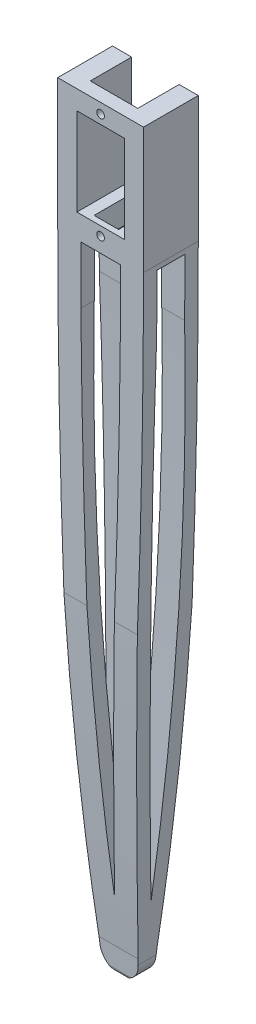
SolidWorks part; units mm, degrees
ref_plane "Front Plane" through (0, 0, 0) normal (0, 0, 1) x (1, 0, 0)
ref_plane "Top Plane" through (0, 0, 0) normal (0, 1, 0) x (1, 0, 0)
ref_plane "Right Plane" through (0, 0, 0) normal (1, 0, 0) x (0, 0, -1)
sketch "Sketch1" plane through (0, 0, 0) normal (0, 0, 1) x (1, 0, 0)
  line L0 (0, -16.45) -> (0, -173.55) construction
  line L1 (-6.2, 16.45) -> (6.2, 16.45)
  line L2 (-11.2, 11.45) -> (-11.2, -16.45)
  line L4 (11.2, 11.45) -> (11.2, -16.45)
  line L5 (-11.2, 16.45) -> (11.2, -16.45) construction
  line L6 (-11.2, -16.45) -> (11.2, 16.45) construction
  arc A1 (-5, -178.55) -> (5, -178.55) centre (0, -178.55) ccw
  arc A2 (-11.2, -16.45) -> (-5, -178.55) centre (2110.9653, -16.45) ccw
  arc A3 (11.2, -16.45) -> (5, -178.55) centre (-2110.9653, -16.45) cw
  arc A4 (11.2, 11.45) -> (6.2, 16.45) centre (6.2, 11.45) ccw
  arc A5 (-6.2, 16.45) -> (-11.2, 11.45) centre (-6.2, 11.45) ccw
  point P0 (0, 0)
  dimension "D4" = 5
  dimension "D1" = 32.9
  dimension "D2" = 22.4
  dimension "D3" = 162.1
extrude "Boss-Extrude2" add sketch "Sketch1" along normal blind 5
sketch "Sketch4" plane through (0, 0, 5) normal (0, 0, 1) x (1, 0, 0)
  line L1 (-6.2, 11.45) -> (6.2, 11.45)
  line L2 (-6.2, 11.45) -> (-6.2, -11.45)
  line L3 (-6.2, -11.45) -> (6.2, -11.45)
  line L4 (6.2, 11.45) -> (6.2, -11.45)
  line L5 (-6.2, 11.45) -> (6.2, -11.45) construction
  line L6 (-6.2, -11.45) -> (6.2, 11.45) construction
  point P0 (0, 0)
  dimension "D1" = 22.9
  dimension "D2" = 12.4
extrude "Cut-Extrude1" cut sketch "Sketch4" against normal blind 5
sketch "Sketch5" plane through (0, 0, 5) normal (0, 0, 1) x (1, 0, 0)
  line L0 (0, 0) -> (0, 13.8) construction
  line L1 (0, 0) -> (0, -13.8) construction
  circle A0 centre (0, 13.8) radius 1
  circle A1 centre (0, -13.8) radius 1
  dimension "D1" = 13.8
  dimension "D2" = 13.8
extrude "Cut-Extrude2" cut sketch "Sketch5" against normal blind 5
sketch3d "3DSketch1"
  line L6 (-5.1604, -32.6864, 5) -> (5.1604, -32.6864, 5)
  spline S2 degree 5 poles (-5.1604, -32.6864, 5) (-5.1261, -37.5289, 5) (-5.0708, -42.3713, 5) (-4.9981, -47.2135, 5) (-4.7659, -60.1446, 5) (-4.4569, -73.0738, 5) (-4.2293, -81.1606, 5) (-3.6967, -97.3316, 5) (-2.9925, -113.496, 5) (-2.6018, -121.5766, 5) (-1.8933, -135.0415, 5) (-1.1015, -148.5022, 5) (-0.7667, -153.8853, 5) (-0.4048, -159.3358, 5) (-0.0148, -164.7842, 5) (-0.0099, -164.8531, 5) (-0.0049, -164.922, 5) (0, -164.9909, 5) knots 0.10922 0.10922 0.10922 0.10922 0.10922 0.10922 0.272094 0.272094 0.272094 0.544187 0.544187 0.544187 0.816281 0.816281 0.816281 0.997676 0.997676 0.997676 1 1 1 1 1 1
  spline S3 degree 5 poles (0, -164.9909, 5) (0.0049, -164.922, 5) (0.0099, -164.8531, 5) (0.0148, -164.7842, 5) (0.4048, -159.3358, 5) (0.7667, -153.8853, 5) (1.1015, -148.5022, 5) (1.8933, -135.0415, 5) (2.6018, -121.5766, 5) (2.9925, -113.496, 5) (3.6967, -97.3316, 5) (4.2293, -81.1606, 5) (4.4569, -73.0738, 5) (4.7659, -60.1446, 5) (4.9981, -47.2135, 5) (5.0708, -42.3713, 5) (5.1261, -37.5289, 5) (5.1604, -32.6864, 5) knots 0 0 0 0 0 0 0.002324 0.002324 0.002324 0.183719 0.183719 0.183719 0.455813 0.455813 0.455813 0.727906 0.727906 0.727906 0.89078 0.89078 0.89078 0.89078 0.89078 0.89078
extrude "Cut-Extrude3" cut sketch "3DSketch1" along direction (0, 0, -1) on the side against the normal blind 5
sketch "Sketch6" plane through (0, 0, 0) normal (0, 0, -1) x (-1, 0, 0)
  line L0 (0, 0) -> (-11.2, 0) construction
  line L1 (-11.2, -16.45) -> (-11.2, 11.45) construction
  line L2 (0, 0) -> (11.2, 0) construction
  line L3 (11.2, 11.45) -> (11.2, -16.45) construction
  line L4 (-11.2, 3.2511) -> (-6.2, 3.2511) construction
  line L5 (-6.2, -11.45) -> (-6.2, 11.45) construction
  line L6 (-8.7, 3.2511) -> (-8.7, 0) construction
  line L7 (6.2, 3.2511) -> (11.2, 3.2511) construction
  line L8 (6.2, 11.45) -> (6.2, -11.45) construction
  line L9 (8.7, 3.2511) -> (8.7, 0) construction
  line L11 (-11.2, 11.45) -> (-6.2, 11.45)
  line L12 (-11.2, 11.45) -> (-11.2, -11.45)
  line L13 (-11.2, -11.45) -> (-6.2, -11.45)
  line L14 (-6.2, 11.45) -> (-6.2, -11.45)
  line L15 (-11.2, 11.45) -> (-6.2, -11.45) construction
  line L16 (-11.2, -11.45) -> (-6.2, 11.45) construction
  line L17 (6.2, 11.45) -> (11.2, 11.45)
  line L18 (6.2, 11.45) -> (6.2, -11.45)
  line L19 (6.2, -11.45) -> (11.2, -11.45)
  line L20 (11.2, 11.45) -> (11.2, -11.45)
  line L21 (6.2, 11.45) -> (11.2, -11.45) construction
  line L22 (6.2, -11.45) -> (11.2, 11.45) construction
  dimension "D1" = 22.9
  dimension "D2" = 22.9
extrude "Boss-Extrude3" add sketch "Sketch6" along normal blind 12.3
sketch "Sketch7" plane through (0, 0, -12.3) normal (0, 0, -1) x (-1, 0, 0)
  line L0 (8.8805, 0) -> (8.8805, 6) construction
  circle A0 centre (-8.6658, 0) radius 1
  circle A1 centre (8.8805, 0) radius 1
  circle A2 centre (8.8805, 6) radius 1
  dimension "D1" = 6
extrude "Cut-Extrude4" cut sketch "Sketch7" against normal blind 5
sketch "Sketch8" plane through (0, 0, 0) normal (0, 0, -1) x (-1, 0, 0)
  line L15 (11.2, -16.45) -> (11.2, -11.45)
  line L16 (11.2, -11.45) -> (6.2, -11.45)
  line L17 (6.2, -11.45) -> (-6.2, -11.45)
  line L18 (-6.2, -11.45) -> (-11.2, -11.45)
  line L19 (-11.2, -11.45) -> (-11.2, -16.45)
  line L20 (11.2, -16.45) -> (11.2, -11.45)
  line L21 (11.2, -11.45) -> (6.2, -11.45)
  line L22 (6.2, -11.45) -> (-6.2, -11.45)
  line L23 (-6.2, -11.45) -> (-11.2, -11.45)
  line L24 (-11.2, -11.45) -> (-11.2, -16.45)
  arc A9 (-11.2, -16.45) -> (-5, -178.55) centre (2110.9653, -16.45) ccw
  arc A10 (-5, -178.55) -> (5, -178.55) centre (0, -178.55) ccw
  arc A11 (5, -178.55) -> (11.2, -16.45) centre (-2110.9653, -16.45) ccw
  arc A12 (-11.2, -16.45) -> (-5, -178.55) centre (2110.9653, -16.45) ccw
  arc A13 (-5, -178.55) -> (5, -178.55) centre (0, -178.55) ccw
  arc A14 (5, -178.55) -> (11.2, -16.45) centre (-2110.9653, -16.45) ccw
  dimension "D1" = 0
extrude "Boss-Extrude4" add sketch "Sketch8" along normal up to surface (12.3 mm away) up to face at (7.6658, 0, -12.3)
sketch "Sketch10" plane through (0, 0, 0) normal (0, 0, 1) x (1, 0, 0)
  line L2 (5.1604, -32.6864) -> (-5.1604, -32.6864)
  line L3 (5.1604, -32.6864) -> (-5.1604, -32.6864)
  spline S4 degree 5 poles (2742.061, 925.339) (1124.3728, 747.4592) (298.2396, 555.4175) (6.2629, 354.0921) (-9.5551, 140.2539) (-4.4569, -73.0738) (-4.2293, -81.1606) (-3.6967, -97.3316) (-2.9925, -113.496) (-2.6018, -121.5766) (-1.8933, -135.0415) (-1.1015, -148.5022) (-0.7667, -153.8853) (8.5195, -293.7189) (36.2296, -432.1823) (-203.7971, -585.1501) (-996.0841, -778.6215) (2070.6534, 438.815) knots -6.632632 -6.632632 -6.632632 -6.632632 -6.632632 -6.632632 0.272094 0.272094 0.272094 0.544187 0.544187 0.544187 0.816281 0.816281 0.816281 0.997676 0.997676 0.997676 5.529664 5.529664 5.529664 5.529664 5.529664 5.529664 only from (-5.1604, -32.6864) to (0, -164.9909)
  spline S5 degree 5 poles (-2591.2367, -1178.5003) (505.7514, -640.2869) (94.1134, -500.1546) (-26.7405, -381.6628) (-6.8269, -268.2322) (0.7667, -153.8853) (1.1015, -148.5022) (1.8933, -135.0415) (2.6018, -121.5766) (2.9925, -113.496) (3.6967, -97.3316) (4.2293, -81.1606) (4.4569, -73.0738) (9.5551, 140.2541) (-6.2629, 354.0925) (-298.2404, 555.4181) (-1124.376, 747.46) (-2742.0685, 925.3399) knots -3.670581 -3.670581 -3.670581 -3.670581 -3.670581 -3.670581 0.002324 0.002324 0.002324 0.183719 0.183719 0.183719 0.455813 0.455813 0.455813 0.727906 0.727906 0.727906 7.632639 7.632639 7.632639 7.632639 7.632639 7.632639 only from (0, -164.9909) to (5.1604, -32.6864)
  spline S6 degree 5 poles (-5.1604, -32.6864) (-5.1261, -37.5289) (-5.0708, -42.3713) (-4.9981, -47.2135) (-4.7659, -60.1446) (-4.4569, -73.0738) (-4.2293, -81.1606) (-3.6967, -97.3316) (-2.9925, -113.496) (-2.6018, -121.5766) (-1.8933, -135.0415) (-1.1015, -148.5022) (-0.7667, -153.8853) (-0.4048, -159.3358) (-0.0148, -164.7842) (-0.0099, -164.8531) (-0.0049, -164.922) (0, -164.9909) knots 0.10922 0.10922 0.10922 0.10922 0.10922 0.10922 0.272094 0.272094 0.272094 0.544187 0.544187 0.544187 0.816281 0.816281 0.816281 0.997676 0.997676 0.997676 1 1 1 1 1 1
  spline S7 degree 5 poles (0, -164.9909) (0.0049, -164.922) (0.0099, -164.8531) (0.0148, -164.7842) (0.4048, -159.3358) (0.7667, -153.8853) (1.1015, -148.5022) (1.8933, -135.0415) (2.6018, -121.5766) (2.9925, -113.496) (3.6967, -97.3316) (4.2293, -81.1606) (4.4569, -73.0738) (4.7659, -60.1446) (4.9981, -47.2135) (5.0708, -42.3713) (5.1261, -37.5289) (5.1604, -32.6864) knots 0 0 0 0 0 0 0.002324 0.002324 0.002324 0.183719 0.183719 0.183719 0.455813 0.455813 0.455813 0.727906 0.727906 0.727906 0.89078 0.89078 0.89078 0.89078 0.89078 0.89078
  dimension "D1" = 0
extrude "Cut-Extrude5" cut sketch "Sketch10" against normal blind 121
sketch "Sketch12" plane through (0, 0, 0) normal (1, 0, 0) x (0, 0, -1)
  line L2 (3.65, -183.55) -> (3.65, -164.9909) construction
  line L3 (-5, -183.55) -> (12.3, -183.55) construction
  line L6 (0, -32.6864) -> (7.3, -32.6864)
  line L7 (3.65, -32.6864) -> (3.65, -164.9909) construction
  arc A0 (0, -32.6864) -> (3.65, -164.9909) centre (1196.4285, -65.8821) ccw
  arc A1 (7.3, -32.6864) -> (3.65, -164.9909) centre (-1189.1285, -65.8821) cw
extrude "Cut-Extrude7" cut sketch "Sketch12" against normal through all
sketch "Sketch14" plane through (0, 0, 0) normal (1, 0, 0) x (0, 0, -1)
  line L0 (7.3, -32.6864) -> (0, -32.6864)
  arc A0 (7.3, -32.6864) -> (3.65, -164.9909) centre (-1189.1285, -65.8821) cw
  arc A1 (0, -32.6864) -> (3.65, -164.9909) centre (1196.4285, -65.8821) ccw
extrude "Cut-Extrude8" cut sketch "Sketch14" along normal blind 121
sketch "Sketch15" plane through (0, 0, 0) normal (1, 0, 0) x (0, 0, -1)
  line L6 (12.3019, -32.6864) -> (24.1567, -32.6864)
  line L7 (24.1567, -32.6864) -> (24.1567, -183.55)
  line L8 (24.1567, -183.55) -> (5.6261, -183.55)
  line L9 (-5.0019, -32.6864) -> (-15.6441, -32.6864)
  line L10 (-15.6441, -32.6864) -> (-15.6441, -183.55)
  line L11 (1.6739, -183.55) -> (-15.6441, -183.55)
  arc A2 (12.3019, -32.6864) -> (7.1191, -182.1952) centre (-1189.1285, -65.8821) cw
  arc A3 (-5.0019, -32.6864) -> (0.1809, -182.1952) centre (1196.4285, -65.8821) ccw
  arc A6 (5.6261, -183.55) -> (7.1191, -182.1952) centre (5.6261, -182.05) ccw
  arc A7 (1.6739, -183.55) -> (0.1809, -182.1952) centre (1.6739, -182.05) cw
  dimension "D2" = 1.5
extrude "Cut-Extrude12" cut sketch "Sketch15" against normal mid plane 121
sketch "Sketch16" plane through (0, -11.45, 0) normal (0, 1, 0) x (1, 0, 0)
  line L8 (-3.2, -2) -> (3.2, -2)
  line L9 (3.2, -2) -> (3.2, 9.3)
  line L10 (3.2, 9.3) -> (-3.2, 9.3)
  line L11 (-3.2, 9.3) -> (-3.2, -2)
  line L12 (-3.2, -2) -> (3.2, -2)
  line L13 (3.2, -2) -> (3.2, 9.3)
  line L14 (3.2, 9.3) -> (-3.2, 9.3)
  line L15 (-3.2, 9.3) -> (-3.2, -2)
  dimension "D1" = 3
extrude "Cut-Extrude13" cut sketch "Sketch16" against normal up to surface (21.2364 mm away) contours L12 L13 L14 L15
sketch "Sketch21" plane through (0, 0, 5) normal (0, 0, 1) x (1, 0, 0)
  line L0 (5.1604, -32.6864) -> (-5.1604, -32.6864) construction
  line L1 (0, -32.6864) -> (0, -17.6864) construction
  line L3 (-5.1604, -32.6864) -> (5.1604, -32.6864)
  line L4 (-5.1604, -32.6864) -> (-5.1604, -17.6864)
  line L5 (-5.1604, -17.6864) -> (5.1604, -17.6864)
  line L6 (5.1604, -32.6864) -> (5.1604, -17.6864)
  dimension "D1" = 15
extrude "Cut-Extrude14" cut sketch "Sketch21" against normal through all
sketch "Sketch23" plane through (-5.1604, 0, 0) normal (1, 0, 0) x (0, 0, -1)
  line L1 (0, -32.6864) -> (7.3, -32.6864)
  line L2 (0, -32.6864) -> (0, -17.6864)
  line L3 (0, -17.6864) -> (7.3, -17.6864)
  line L4 (7.3, -32.6864) -> (7.3, -17.6864)
  dimension "D1" = 15
extrude "Cut-Extrude15" cut sketch "Sketch23" against normal through all both and the other way through all
sketch "Sketch24" plane through (0, 11.45, 0) normal (0, 1, 0) x (1, 0, 0)
  line L1 (6.2, 0) -> (11.2, 0)
  line L2 (6.2, 0) -> (6.2, 12.3)
  line L3 (6.2, 12.3) -> (11.2, 12.3)
  line L4 (11.2, 0) -> (11.2, 12.3)
  line L5 (-6.2, 0) -> (-11.2, 0)
  line L6 (-6.2, 0) -> (-6.2, 12.3)
  line L7 (-6.2, 12.3) -> (-11.2, 12.3)
  line L8 (-11.2, 0) -> (-11.2, 12.3)
extrude "Boss-Extrude5" add sketch "Sketch24" along normal up to surface (5 mm away) up to face at (0, 16.45, 2.5)
sketch "Sketch25" plane through (11.2, 0, 0) normal (1, 0, 0) x (0, 0, -1)
  line L1 (-5, 11.45) -> (12.3, 11.45)
  line L2 (-5, 11.45) -> (-5, 16.45)
  line L3 (-5, 16.45) -> (12.3, 16.45)
  line L4 (12.3, 11.45) -> (12.3, 16.45)
extrude "Boss-Extrude6" add sketch "Sketch25" against normal up to next
sketch "Sketch26" plane through (-11.2, 0, 0) normal (-1, 0, 0) x (0, 0, 1)
  line L1 (5, 11.45) -> (0, 11.45)
  line L2 (5, 11.45) -> (5, 16.45)
  line L3 (5, 16.45) -> (0, 16.45)
  line L4 (0, 11.45) -> (0, 16.45)
extrude "Boss-Extrude7" add sketch "Sketch26" against normal up to next
sketch "Sketch27" plane through (0, 0, 5) normal (0, 0, 1) x (1, 0, 0)
sketch "Sketch28" plane through (6.2, 0, 0) normal (-1, 0, 0) x (0, 0, 1)
sketch "Sketch30" plane through (-11.2, 0, 0) normal (-1, 0, 0) x (0, 0, 1)
  line L0 (-6.1017, -177.05) -> (-5.6939, -182.623)
  line L1 (-4.6966, -183.55) -> (-2.6034, -183.55)
  line L2 (-1.6061, -182.623) -> (-1.1983, -177.05)
  line L3 (-10.8, -17.95) -> (-10.8, 16.45)
  line L8 (-10.8, -17.95) -> (-10.8, -99.1262)
  line L9 (-6.1017, -177.05) -> (-1.1983, -177.05)
  line L10 (3.5, -99.1262) -> (3.5, -17.95)
  line L11 (3.5, -17.95) -> (-10.8, -17.95)
  line L12 (-10.8, -17.95) -> (-10.8, -99.1262)
  line L14 (3.5, -99.1262) -> (3.5, -17.95)
  line L28 (5, 16.45) -> (-12.3, 16.45) construction
  line L29 (-10.8, 16.45) -> (3.5, 16.45)
  line L30 (3.5, 16.45) -> (3.5, -17.95)
  arc A0 (-2.6034, -183.55) -> (-1.6061, -182.623) centre (-2.6034, -182.55) ccw
  arc A1 (-4.6966, -183.55) -> (-5.6939, -182.623) centre (-4.6966, -182.55) cw
  arc A4 (-10.8, -99.1262) -> (-6.1017, -177.05) centre (1189.1285, -65.8821) ccw
  arc A5 (-1.1983, -177.05) -> (3.5, -99.1262) centre (-1196.4285, -65.8821) ccw
  arc A6 (-10.8, -99.1262) -> (-6.1017, -177.05) centre (1189.1285, -65.8821) ccw
  arc A7 (-1.1983, -177.05) -> (3.5, -99.1262) centre (-1196.4285, -65.8821) ccw
  point P4 (-1.6739, -183.55)
  point P7 (-5.6261, -183.55)
  dimension "D2" = 1
  dimension "D1" = 1.5
extrude "Cut-Extrude16" cut sketch "Sketch30" against normal through all flip side to cut
